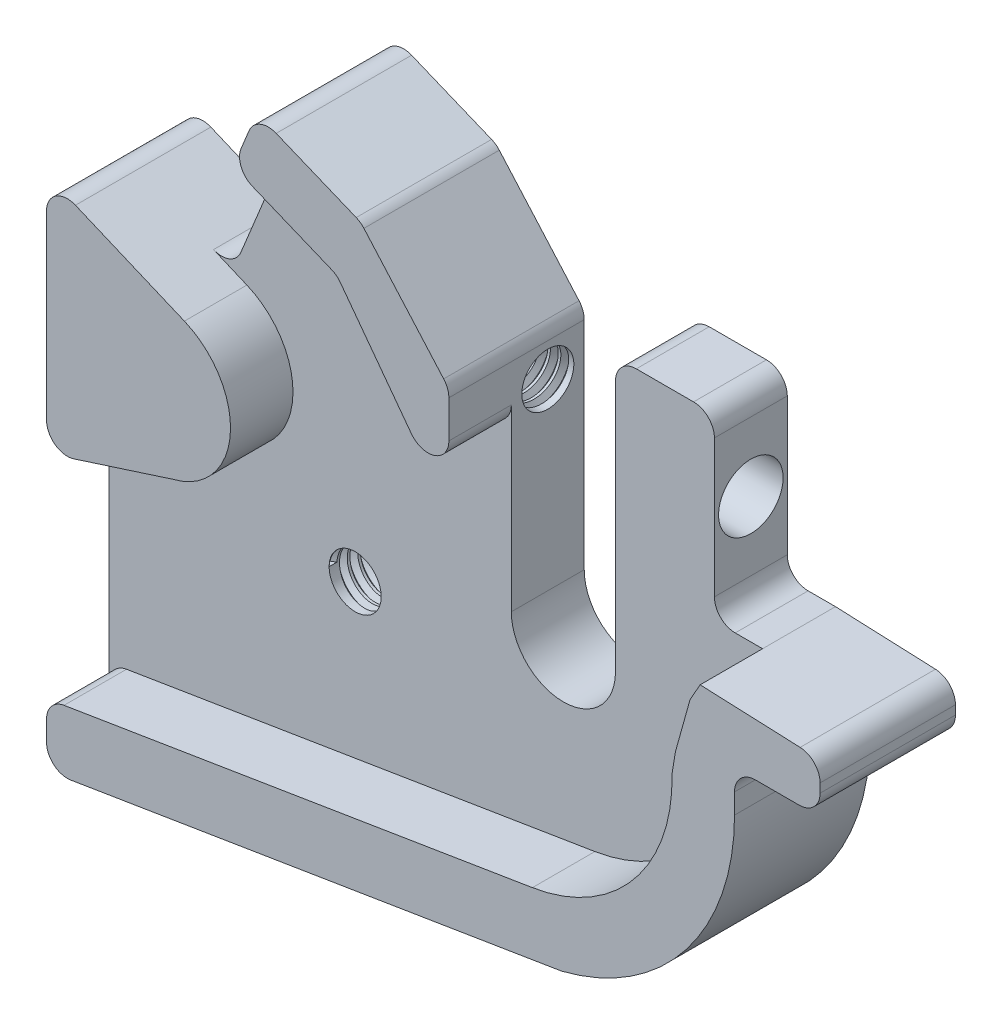
SolidWorks part; units mm, degrees
ref_plane "Front Plane" through (0, 0, 0) normal (0, 0, 1) x (1, 0, 0)
ref_plane "Top Plane" through (0, 0, 0) normal (0, 1, 0) x (1, 0, 0)
ref_plane "Right Plane" through (0, 0, 0) normal (1, 0, 0) x (0, 0, -1)
sketch "Sketch1" plane through (0, 0, 0) normal (0, 0, 1) x (1, 0, 0)
  line L0 (-48.8998, -64.1664) -> (-34.4801, 53.9567) construction
  line L3 (0, 51.4823) -> (78.4652, 51.4823)
  line L4 (78.4652, 0) -> (78.4652, 51.4823)
  line L5 (-0.9054, 14.8469) -> (9.0946, 14.8469)
  line L6 (9.0946, 14.8469) -> (9.0946, -2.1531)
  line L7 (9.0946, -2.1531) -> (-0.9054, -2.1531)
  line L8 (-0.9054, -2.1531) -> (-0.9054, 14.8469)
  line L9 (-11.6542, 28.4583) -> (-0.9054, 14.02)
  line L10 (-52.5896, 45.2866) -> (-11.6542, 28.4583)
  line L11 (9.0946, 14.8469) -> (9.0946, 29.052)
  line L12 (9.0946, 29.052) -> (18.5946, 29.052)
  line L13 (-61.5112, 32.1478) -> (-26.3036, 17.3197)
  line L14 (-26.3036, 17.3197) -> (-29.1124, 10.6505)
  line L15 (-29.1124, 10.6505) -> (-31.9213, 3.9813)
  line L16 (-70.304, -10.1797) -> (-26.4323, 3.9286)
  line L17 (-39.5424, 22.8954) -> (-39.5424, -0.2874)
  line L18 (-26.4323, 3.9286) -> (-29.1124, 10.6505)
  line L19 (-29.1124, 10.6505) -> (-31.7926, 17.3724)
  line L20 (-74.2907, -26.3461) -> (-1.036, -14.4136)
  line L21 (-1.036, -14.4136) -> (7.1186, -13.0853)
  line L22 (23.2246, 11.8381) -> (22.2572, 10.123)
  line L23 (23.2246, 11.8381) -> (34.7443, 11.3546)
  line L24 (-0.9054, 14.8469) -> (-0.9054, 20.5391)
  line L25 (-19.3381, 38.1043) -> (-8.9222, 33.8224)
  line L26 (-11.6542, 28.4583) -> (-9.3728, 34.0076)
  line L27 (-7.3088, 22.6214) -> (-2.496, 26.2043)
  line L28 (-2.496, 26.2043) -> (-9.3728, 34.0076)
  line L29 (-70.3938, -25.7113) -> (-69.6167, -30.4821)
  line L30 (-39.5424, -20.686) -> (-39.5424, -26.686)
  line L31 (26.529, 2.6512) -> (26.529, -15.9236)
  line L32 (27.019, 6.583) -> (34.7443, 6.583)
  line L33 (34.7443, 6.583) -> (34.7443, 11.3546)
  line L34 (-11.6542, 28.4583) -> (-8.9222, 28.4583)
  line L35 (-70.3938, -25.7113) -> (-70.304, -10.1797)
  line L36 (18.5946, 29.052) -> (18.5946, 11.8381)
  line L37 (-39.5424, -0.2874) -> (-39.5424, -20.686)
  line L38 (-39.5424, 22.8954) -> (-39.5424, 39.923)
  line L39 (22.2572, 10.123) -> (21.4546, 7.2463)
  line L40 (21.4546, 7.2463) -> (20.8501, 5.08)
  line L41 (20.8501, 5.08) -> (20.5233, 3.0772)
  line L42 (-8.9222, 28.4583) -> (-8.9222, 25.2921)
  line L43 (-19.3381, 38.1043) -> (-21.6194, 32.5549)
  line L44 (-0.9054, 20.5391) -> (-0.9054, 24.0677)
  line L45 (-2.496, 26.2043) -> (-0.9054, 24.3993)
  line L46 (-21.6194, 32.5549) -> (-27.6495, 17.8865)
  line L47 (-39.5424, -26.686) -> (29.4812, -15.4427)
  line L48 (4.5907, 2.6512) -> (20.529, 2.6512) construction
  line L49 (20.529, 2.6512) -> (26.529, 2.6512) construction
  line L50 (26.529, 2.6512) -> (26.529, 6.583)
  line L51 (26.529, 6.583) -> (27.019, 6.583)
  line L52 (-0.9054, 24.3993) -> (-0.9054, 24.0677)
  line L53 (18.5946, 11.8381) -> (23.2246, 11.8381)
  line L54 (4.0946, -2.1531) -> (-15.9054, -2.1531)
  circle A0 centre (4.0946, 2.8469) radius 5
  circle A1 centre (4.0946, 9.8469) radius 5
  circle A2 centre (-29.1124, 10.6505) radius 7.2365
  circle A3 centre (4.5907, 2.6512) radius 15.9383
  circle A4 centre (4.5907, 2.6512) radius 21.9383
  circle A5 centre (-15.9054, -2.1531) radius 3
  dimension "D4" = 9.5
  dimension "D7" = 6
  dimension "D1" = 119
  dimension "D2" = 10
  dimension "D3" = 17
  dimension "D5" = 18
  dimension "D6" = 6
extrude "Boss-Extrude2" add sketch "Sketch1" along normal blind 7 contours A5 A4 L9 L10 L46 L13 A2 L16 L37 L20 | A2 L13 L17 L16 | L25 L43 L10 L26 | L27 L28 L26 L9 | A4 L44 L52 L45 L27 L9 | A5 L54 A3 L9 A4 | A5 A4 L20 L21 A3 L54 | A3 L11 L6 L7 L54 | L9 A3 L54 L8 | A0 L8 L7 | A0 L7 L6 | L44 A4 L9 A3 L24 | L24 A3 L9 L8 | L36 A4 L11 A3 L41 L40 L39 L22 L53 | A4 L36 L12 L11 | L20 A4 L47 L23 L22 L39 L40 L41 A3 L21 | A4 L50 L51 L32 L33 L23 | A4 L20 L30 L47 | A4 A5 | A5 A4 | A2 region at (-1.579, 16.1313, 0) region at (-5.5514, 5.8811, 0) region at (-2.9873, 20.47, 0) region at (9.5356, 16.3934, 0) region at (-11.4558, 10.3377, 0) region at (15.4515, 16.6771, 0) region at (7.9778, -1.0363, 0) region at (0.2115, -1.0363, 0) region at (-23.7133, 1.7412, 0) region at (-3.9237, 23.8565, 0) region at (-8.3873, -9.8482, 0) region at (14.3748, 25.5507, 0) region at (21.1435, 4.0041, 0) region at (-7.5395, 27.8934, 0) region at (-15.0859, -1.961, 0) region at (-17.5867, -2.5472, 0) region at (-15.4961, 33.2813, 0) region at (30.0023, 9.1107, 0) region at (-20.9546, -20.8236, 0) region at (-36.3421, 11.3624, 0)
extrude "Boss-Extrude3" add sketch "Sketch1<7>" along normal blind 13 contours A2 L13 L17 L16 | L25 L43 L10 L26 | L27 L28 L26 L9 | A4 L44 L27 L9 | L44 A4 L9 A3 L24 | L24 A3 L9 L8 | A4 L20 L30 L47 | L20 A4 L47 L23 L22 L39 L40 L41 A3 L21 | A4 L50 L51 L32 L33 L23 | A2 region at (-1.579, 16.1313, 0) region at (-2.9873, 20.47, 0) region at (-3.9237, 23.8565, 0) region at (21.1435, 4.0041, 0) region at (-7.5395, 27.8934, 0) region at (-15.4961, 33.2813, 0) region at (30.0023, 9.1107, 0) region at (-20.9546, -20.8236, 0) region at (-36.3421, 11.3624, 0)
sketch "Sketch1<7>" plane through (0, 0, 0) normal (0, 0, 1) x (1, 0, 0) same geometry as "Sketch1"
sketch "Sketch2" plane through (18.5946, 0, 0) normal (1, 0, 0) x (0, 0, -1)
  line L0 (-3.5, 29.052) -> (-3.5, 20.445) construction
  line L1 (-7, 29.052) -> (0, 29.052) construction
  line L2 (-7, 20.445) -> (-3.5, 20.445) construction
  line L3 (-7, 29.052) -> (-7, 11.8381) construction
  circle A0 centre (-3.5, 20.445) radius 3.1
  dimension "D1" = 6.2
hole_wizard "Tap Drill for M6x1.0 Tap3" positions "3DSketch3" profile "Sketch7" hole size "M6x1.0" standard "ANSI Metric"
sketch3d "3DSketch3"
  point P0 (18.5946, 20.445, 3.5)
sketch "Sketch7" plane through (18.5946, 20.445, 3.5) normal (0, 1, 0) x (0, 0, -1)
  line L0 (0, 0) -> (0, 44.5022)
  line L1 (0, 44.5022) -> (2.5, 43)
  line L2 (2.5, 43) -> (2.5, 0)
  line L5 (2.5, 0) -> (0, 0)
  line L10 (0, 44.5022) -> (-2.5, 43) construction
  line L11 (0, -6.35) -> (0, 107.95) construction
  dimension "Hole Dia." = 5
  dimension "Hole Depth" = 43
  dimension "Drill Angle" = 118
fillet "Fillet1" radius 2 17 edges at (-39.5424, -20.686, 10) (-39.5424, -0.2874, 10) (-39.5424, -26.686, 6.5) (34.7443, 6.583, 6.5) (34.7443, 11.3546, 6.5) (-0.9054, 14.02, 10) (-21.6194, 32.5549, 10) (-19.3381, 38.1043, 6.5) (-39.5424, 22.8954, 6.5) (-27.6495, 17.8865, 3.5) (-9.3728, 34.0076, 6.5) (9.0946, 29.052, 3.5) (18.5946, 29.052, 3.5) (18.5946, 11.8381, 3.5) (-0.9054, 24.3993, 6.5) (26.529, 6.583, 6.5) (-11.6542, 28.4583, 10)
hole_wizard "Tap Drill for M6x1.0 Tap2" positions "3DSketch2" profile "Sketch5" hole size "M6x1.0" standard "ANSI Metric" end condition through all
sketch3d "3DSketch2"
  line L0 (4.0946, -2.1531, 7) -> (-15.9054, -2.1531, 7)
  arc A0 (-0.9054, 2.8469, 7) -> (9.0946, 2.8469, 7) centre (4.0946, 2.8469, 7) ccw construction
  point P0 (-15.9054, -2.1531, 7)
  point P8 (4.0946, 2.8469, 12)
  point P10 (0, 0, 0)
  point P11 (-15.9054, -2.1531, 10)
  dimension "D1" = 20
sketch "Sketch5" plane through (-15.9054, -2.1531, 7) normal (1, 0, 0) x (0, -1, 0)
  line L0 (0, 0) -> (0, 7)
  line L1 (0, 7) -> (2.5, 7)
  line L2 (2.5, 7) -> (2.5, 0)
  line L5 (2.5, 0) -> (0, 0)
  line L11 (0, -6.35) -> (0, 107.95) construction
  dimension "Thru Hole Dia." = 5
  dimension "Thru Hole Depth" = 7
thread "Thread1" pitch 1 method cut profile "Thread Profile2" start angle 0, offset 0, length 23, pitch 1, diameter 5
ref_plane "Plane2" through (-0.9054, 20.445, 6) normal (0, -1, 0) x (0, 0, 1)
sketch "Thread Profile2" plane through (-0.9054, 20.445, 6) normal (0, -1, 0) x (0, 0, 1)
  line L0 (0, 0) -> (0, 1) construction
  line L1 (0, 0) -> (0.5413, 0.3125)
  line L2 (0.5413, 0.3125) -> (0.5413, 0.4375)
  line L3 (0.5413, 0.4375) -> (0, 0.75)
  line L4 (0.5413, 0.375) -> (0, 0.375) construction
  line L11 (0, 0) -> (0, 0.75)
  point P2 (0, 0)
  dimension "Pitch" = 1
  dimension "Profile_Angle" = 60
  dimension "Profile_Land" = 0.125
  dimension "Profile_Height" = 0.5413
extrude "Cut-Extrude2" cut sketch "Sketch2" against normal blind 10 contours A0
thread "Thread2" pitch 1 method cut profile "Thread Profile3" start angle 0, offset 0, length 13, pitch 1, diameter 5
ref_plane "Plane3" through (-18.4054, -2.1531, 7) normal (0, -1, 0) x (-1, 0, 0)
sketch "Thread Profile3" plane through (-18.4054, -2.1531, 7) normal (0, -1, 0) x (-1, 0, 0)
  line L0 (0, 0) -> (0, 1) construction
  line L1 (0, 0) -> (0.5413, 0.3125)
  line L2 (0.5413, 0.3125) -> (0.5413, 0.4375)
  line L3 (0.5413, 0.4375) -> (0, 0.75)
  line L4 (0.5413, 0.375) -> (0, 0.375) construction
  line L11 (0, 0) -> (0, 0.75)
  point P2 (0, 0)
  dimension "Pitch" = 1
  dimension "Profile_Angle" = 60
  dimension "Profile_Land" = 0.125
  dimension "Profile_Height" = 0.5413
